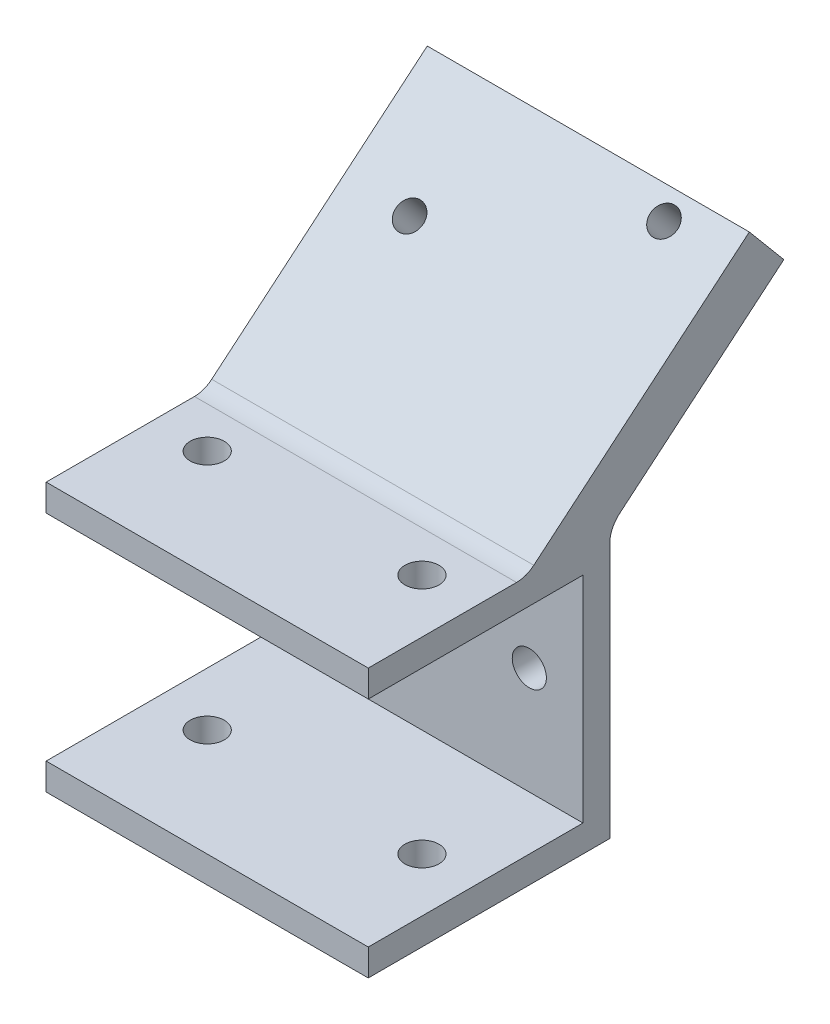
SolidWorks part; units mm, degrees
material "ABS"
ref_plane "Front Plane" through (0, 0, 0) normal (0, 0, 1) x (1, 0, 0)
ref_plane "Top Plane" through (0, 0, 0) normal (0, 1, 0) x (1, 0, 0)
ref_plane "Right Plane" through (0, 0, 0) normal (1, 0, 0) x (0, 0, -1)
sketch "Sketch1" plane through (0, 0, 0) normal (1, 0, 0) x (0, 0, -1)
  line L0 (-12.7, 12.7) -> (12.7, 12.7)
  line L1 (-12.7, -15.875) -> (15.875, -15.875)
  line L2 (-15.875, -15.875) -> (-15.875, 15.875) construction
  line L3 (-12.7, 15.875) -> (15.875, 15.875)
  line L4 (15.875, -15.875) -> (15.875, 15.875)
  line L5 (-15.875, -15.875) -> (15.875, 15.875) construction
  line L6 (-15.875, 15.875) -> (15.875, -15.875) construction
  line L7 (12.7, -12.7) -> (12.7, 12.7)
  line L8 (-12.7, -12.7) -> (12.7, -12.7)
  line L9 (-12.7, -12.7) -> (-12.7, 12.7) construction
  line L10 (-12.7, 12.7) -> (-12.7, 15.875)
  line L12 (-15.875, 15.875) -> (15.875, 15.875) construction
  line L13 (-12.7, -12.7) -> (-12.7, -15.875)
  line L14 (15.875, -15.875) -> (15.875, 15.875) construction
  line L15 (-15.875, -15.875) -> (15.875, -15.875) construction
  point P0 (0, 0)
  dimension "D1" = 31.75
  dimension "D2" = 31.75
  dimension "D3" = 3.175
extrude "Boss-Extrude1" add sketch "Sketch1" along normal blind 38.1
sketch "Sketch2" plane through (0, 15.875, 0) normal (0, 1, 0) x (1, 0, 0)
  line L0 (19.05, 15.875) -> (19.05, -12.7) construction
  line L1 (38.1, -12.7) -> (0, -12.7) construction
  line L2 (6.35, 0) -> (31.75, 0) construction
  line L7 (38.1, 15.875) -> (0, 15.875) construction
  circle A0 centre (6.35, 0) radius 2.0193
  circle A1 centre (31.75, 0) radius 2.0193
  point P14 (19.05, 0)
  dimension "D1" = 4.0386
  dimension "D4" = 4.0386
  dimension "D6" = 25.4
  dimension "D7" = 15.875
extrude "Cut-Extrude1" cut sketch "Sketch2" against normal blind 38.862
sketch "Sketch5" plane through (38.1, 0, 0) normal (1, 0, 0) x (0, 0, -1)
  line L0 (15.875, 15.875) -> (36.4582, 33.1462)
  line L1 (15.875, 15.875) -> (36.4581, 15.875) construction
  line L2 (36.4581, 15.875) -> (36.4582, 33.1462) construction
  line L3 (36.4582, 33.1462) -> (32.3765, 38.0106)
  line L4 (32.3765, 38.0106) -> (5.9961, 15.875)
  line L5 (15.875, 15.875) -> (-12.7, 15.875) construction
  line L6 (5.9961, 15.875) -> (15.875, 15.875)
  dimension "D1" = 26.8694
  dimension "D2" = 20.5831
  dimension "D3" = 17.2712
  dimension "D4" = 6.35
extrude "Boss-Extrude2" add sketch "Sketch5" against normal blind 38.1
fillet "Fillet1" radius 3.175 2 edges at (19.05, 15.875, -15.875) (19.05, 15.875, -5.9961)
ref_plane "Plane1" through (19.05, 0, 0) normal (1, 0, 0) x (0, 0, -1)
ref_axis "Axis1" through (31.75, 12.7, 0) along (0, 1, 0)
ref_axis "Axis2" through (6.35, 12.7, 0) along (0, 1, 0)
ref_plane "Plane2" through (0, 0, 0) normal (0, 0, -1) x (-1, 0, 0)
ref_axis "Axis3" through (19.05, 16.0337, 0) along (0, -1, 0)
ref_plane "Plane3" through (0, 0, 0) normal (0, -1, 0) x (-1, 0, 0)
ref_axis "Axis4" through (21.2725, 0, 0) along (-1, 0, 0)
pattern_circular "CirPattern1" count 2 every 90 about axis through (21.2725, 0, 0) along (-1, 0, 0) of "Cut-Extrude1"
sketch "Sketch6" plane through (0, 6.3634, 5.3395) normal (0, 0.766, 0.6428) x (1, 0, 0)
  line L0 (19.05, 49.2346) -> (19.05, 33.3346) construction
  line L2 (5.15, 33.3346) -> (32.95, 33.3346) construction
  line L3 (0, 49.2346) -> (38.1, 49.2346) construction
  line L5 (5.15, 33.3346) -> (5.15, 49.2346) construction
  line L6 (5.15, 49.2346) -> (32.95, 49.2346) construction
  line L7 (32.95, 33.3346) -> (32.95, 49.2346) construction
  line L8 (5.15, 33.3346) -> (32.95, 49.2346) construction
  line L9 (5.15, 49.2346) -> (32.95, 33.3346) construction
  circle A0 centre (7.95, 36.1346) radius 1.625
  circle A1 centre (30.15, 46.4346) radius 1.625
  point P4 (19.05, 41.2846)
  point P9 (19.05, 34.3347)
  dimension "D3" = 3.25
  dimension "D4" = 3.25
  dimension "D1" = 15.9
  dimension "D2" = 15.9
  dimension "D5" = 2.8
  dimension "D6" = 27.8
  dimension "D7" = 2.8
  dimension "D8" = 25
  dimension "D9" = 13.1
extrude "Cut-Extrude2" cut sketch "Sketch6" against normal blind 28.575
